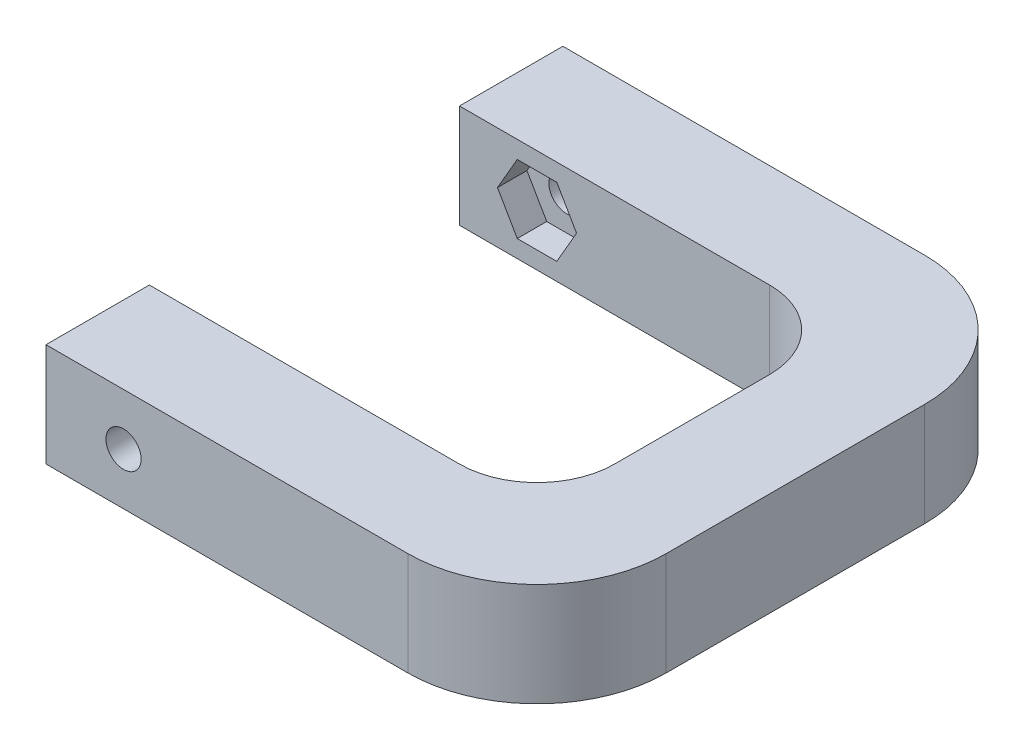
SolidWorks part; units mm, degrees
ref_plane "Front Plane" through (0, 0, 0) normal (0, 0, 1) x (1, 0, 0)
ref_plane "Top Plane" through (0, 0, 0) normal (0, 1, 0) x (1, 0, 0)
ref_plane "Right Plane" through (0, 0, 0) normal (1, 0, 0) x (0, 0, -1)
sketch "Sketch2" plane through (0, 0, 0) normal (0, 1, 0) x (1, 0, 0)
  line L0 (-95, 20) -> (-95, 0)
  line L1 (-95, 0) -> (0, 0)
  line L4 (-95, 20) -> (-20, 20)
  line L5 (0, 0) -> (0, 100)
  line L6 (-20, 20) -> (-20, 80)
  line L7 (-20, 80) -> (-95, 80)
  line L8 (-95, 80) -> (-95, 100)
  line L9 (-95, 100) -> (0, 100)
  dimension "D1" = 20
  dimension "D2" = 75
  dimension "D3" = 20
  dimension "D4" = 60
extrude "Boss-Extrude1" add sketch "Sketch2" along normal blind 20
sketch "Sketch3" plane through (0, 0, -80) normal (0, 0, 1) x (1, 0, 0)
  line L0 (-95, 20) -> (-95, 0) construction
  line L2 (-80, 10) -> (-95, 10) construction
  line L3 (-95, 20) -> (0, 20) construction
  line L4 (-95, 0) -> (0, 0) construction
  circle A0 centre (-80, 10) radius 3.4
  dimension "D1" = 6.8
  dimension "D2" = 15
extrude "Cut-Extrude1" cut sketch "Sketch3" against normal through all both and the other way through all
sketch "Sketch4" plane through (0, 0, -80) normal (0, 0, 1) x (1, 0, 0)
  line L1 (-76.175, 3.3749) -> (-72.35, 10)
  line L2 (-72.35, 10) -> (-76.175, 16.6251)
  line L3 (-76.175, 16.6251) -> (-83.825, 16.6251)
  line L4 (-83.825, 16.6251) -> (-87.65, 10)
  line L5 (-87.65, 10) -> (-83.825, 3.3749)
  line L6 (-83.825, 3.3749) -> (-76.175, 3.3749)
  circle A0 centre (-80, 10) radius 6.6251 construction
  dimension "D1" = 15.3
extrude "Cut-Extrude2" cut sketch "Sketch4" against normal blind 5.7
extrude "Cut-Extrude3" cut sketch "Sketch4<2>" along normal blind 5.7 from surface starting at face at (-76.6, 10, -20)
sketch "Sketch4<2>" plane through (0, 0, -80) normal (0, 0, 1) x (1, 0, 0) same geometry as "Sketch4"
fillet "Fillet1" radius 15 2 edges at (-20, 10, -20) (-20, 10, -80)
fillet "Fillet2" radius 25 2 edges at (0, 10, 0) (0, 10, -100)
